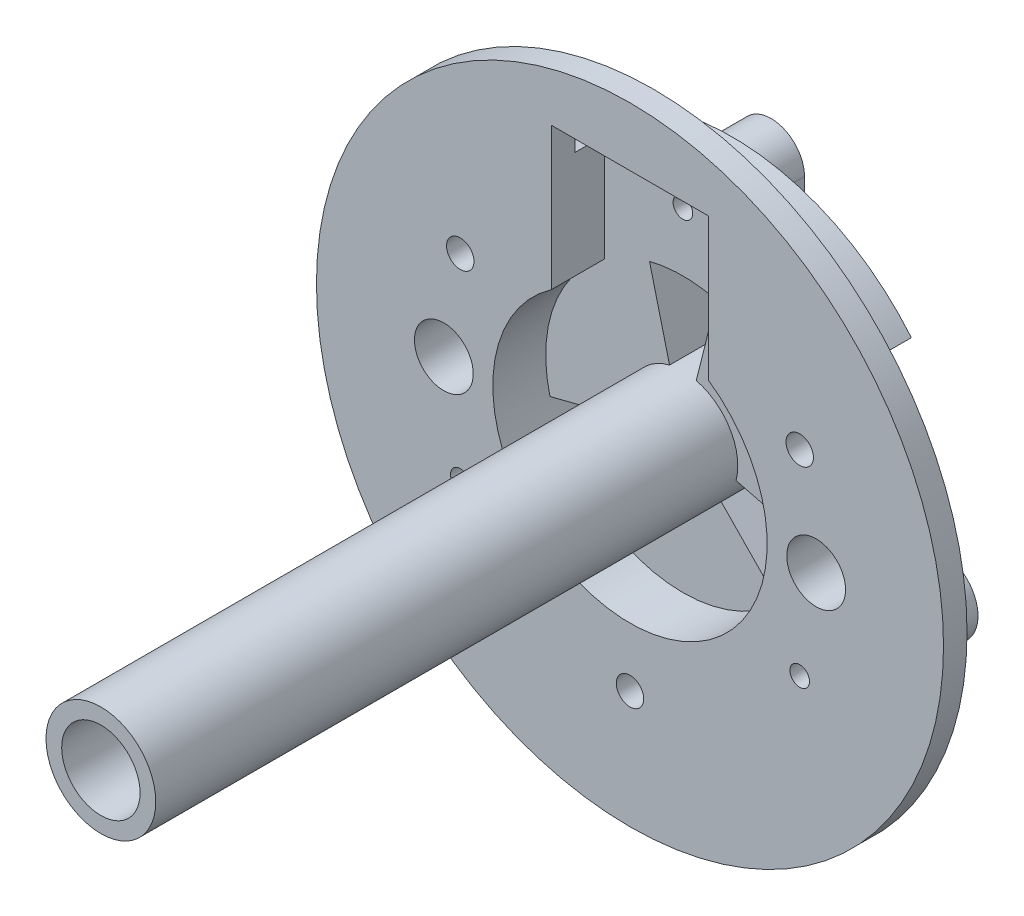
SolidWorks part; units mm, degrees
ref_plane "前视基准面" through (0, 0, 0) normal (0, 0, 1) x (1, 0, 0)
ref_plane "上视基准面" through (0, 0, 0) normal (0, 1, 0) x (1, 0, 0)
ref_plane "右视基准面" through (0, 0, 0) normal (1, 0, 0) x (0, 0, -1)
sketch "草图1" plane through (0, 0, 0) normal (0, 0, 1) x (1, 0, 0)
  circle A0 centre (0, 0) radius 16
extrude "凸台-拉伸1" add sketch "草图1" along normal blind 1.2
sketch "草图2" plane through (0, 0, 1.2) normal (0, 0, 1) x (1, 0, 0)
  circle A0 centre (0, 0) radius 7
extrude "切除-拉伸1" cut sketch "草图2" against normal blind 1.2
sketch "草图3" plane through (0, 0, 1.2) normal (0, 0, 1) x (1, 0, 0)
  circle A2 centre (8.6603, 5) radius 0.7
  circle A3 centre (0, -10) radius 0.7
  circle A4 centre (-8.6603, 5) radius 0.7
extrude "切除-拉伸2" cut sketch "草图3" against normal blind 1.2
sketch "草图4" plane through (0, 0, 0) normal (0, 0, -1) x (-1, 0, 0)
  line L3 (1.7039, 10) -> (1.7039, 5.3952)
  line L16 (-5.5379, -1.0034) -> (-3.6379, -4.2943)
  line L17 (3.6379, -4.2943) -> (5.5379, -1.0034)
  line L18 (1.7039, 5.3952) -> (-1.7039, 5.3952)
  line L19 (-5.5379, -1.0034) -> (-9.6103, -3.3546)
  line L21 (3.6379, -4.2943) -> (7.7103, -6.6454)
  line L25 (-3.6379, -4.2943) -> (-7.7103, -6.6454)
  line L31 (5.5379, -1.0034) -> (9.6103, -3.3546)
  line L32 (-1.7039, 5.3952) -> (-1.7039, 10)
  circle A1 centre (8.6603, -5) radius 0.9
  circle A2 centre (-8.6603, -5) radius 0.9
  circle A3 centre (0, 10) radius 0.9
  arc A4 (1.7039, 10) -> (-1.7039, 10) centre (0, 10) ccw
  arc A5 (7.7103, -6.6454) -> (9.6103, -3.3546) centre (8.6603, -5) ccw
  arc A6 (-9.6103, -3.3546) -> (-7.7103, -6.6454) centre (-8.6603, -5) ccw
extrude "凸台-拉伸2" add sketch "草图4" along normal blind 6
sketch "草图5" plane through (0, 0, 1.2) normal (0, 0, 1) x (1, 0, 0)
  circle A0 centre (0, 0) radius 7
extrude "切除-拉伸3" cut sketch "草图5" against normal blind 11
sketch "草图6" plane through (0, 0, 0) normal (0, 0, -1) x (-1, 0, 0)
  circle A0 centre (0, 0) radius 11.9
  circle A1 centre (0, 0) radius 7
extrude "凸台-拉伸3" add sketch "草图6" along normal blind 4
sketch "草图7" plane through (0, 0, 1.2) normal (0, 0, 1) x (1, 0, 0)
  circle A0 centre (-8.6603, 5) radius 0.7
  circle A1 centre (8.6603, 5) radius 0.7
  circle A2 centre (0, -10) radius 0.7
extrude "切除-拉伸4" cut sketch "草图7" against normal blind 13
sketch "草图8" plane through (0, 0, -4) normal (0, 0, -1) x (-1, 0, 0)
  circle A0 centre (0, 0) radius 2.8
extrude "凸台-拉伸4" add sketch "草图8" against normal blind 33 separate body
sketch "草图9" plane through (0, 0, -4) normal (0, 0, -1) x (-1, 0, 0)
  line L0 (-1.57, -1.6117) -> (-4.8846, -5.0141)
  line L1 (1.57, -1.6117) -> (4.8846, -5.0141)
  line L2 (-2.1808, -0.5539) -> (-6.7846, -1.7232)
  line L3 (-0.5477, 2.1823) -> (-1.7039, 6.7895)
  line L4 (0.5477, 2.1823) -> (1.7039, 6.7895)
  line L5 (2.1808, -0.5539) -> (6.7846, -1.7232)
  arc A0 (-4.8846, -5.0141) -> (4.8846, -5.0141) centre (0, 0) ccw
  arc A1 (-1.7039, 6.7895) -> (-6.7846, -1.7232) centre (0, 0) ccw
  arc A2 (6.7846, -1.7232) -> (1.7039, 6.7895) centre (0, 0) ccw
  arc A3 (2.1808, -0.5539) -> (0.5477, 2.1823) centre (0, 0) ccw
  arc A4 (-1.57, -1.6117) -> (1.57, -1.6117) centre (0, 0) ccw
  arc A5 (-0.5477, 2.1823) -> (-2.1808, -0.5539) centre (0, 0) ccw
extrude "凸台-拉伸5" add sketch "草图9" against normal blind 2.5
sketch "草图10" plane through (0, 0, -4) normal (0, 0, -1) x (-1, 0, 0)
  circle A0 centre (0, 0) radius 1.5
extrude "切除-拉伸5" cut sketch "草图10" against normal blind 33.5
sketch "草图12" plane through (0, 0, 0) normal (1, 0, 0) x (0, 0, -1)
  line L3 (-19.95, -5.0897) -> (-33.7637, -5.0897)
  line L4 (-19.95, -5.0897) -> (-19.95, 5.3715)
  line L5 (-19.95, 5.3715) -> (-33.7637, 5.3715)
  line L6 (-33.7637, -5.0897) -> (-33.7637, 5.3715)
extrude "切除-拉伸6" cut sketch "草图12" against normal mid plane 33.5
sketch "草图13" plane through (0, 0, -4) normal (0, 0, -1) x (-1, 0, 0)
  circle A0 centre (0, -10) radius 2
  circle A1 centre (8.6603, 5) radius 2
  circle A2 centre (-8.6603, 5) radius 2
extrude "切除-拉伸7" cut sketch "草图13" against normal blind 1.5
sketch "草图14" plane through (0, 0, 19.95) normal (0, 0, 1) x (1, 0, 0)
  circle A0 centre (0, 0) radius 2
  circle A1 centre (0, 0) radius 2.8
extrude "凸台-拉伸6" add sketch "草图14" along normal blind 8.25
sketch "草图16" plane through (0, 0, -4) normal (0, 0, -1) x (-1, 0, 0)
  line L3 (0, -10) -> (-2, -10)
  line L4 (-2, -10) -> (-2, -14.1303)
  line L5 (-2, -14.1303) -> (2, -14.1303)
  line L6 (2, -14.1303) -> (2, -10)
  line L7 (2, -10) -> (0, -10)
  line L8 (-9.6603, 3.2679) -> (-8.6603, 5)
  line L9 (-8.6603, 5) -> (-7.6603, 6.7321)
  line L10 (-7.6603, 6.7321) -> (-11.2372, 8.7972)
  line L11 (-11.2372, 8.7972) -> (-13.2372, 5.3331)
  line L12 (-13.2372, 5.3331) -> (-9.6603, 3.2679)
  line L13 (7.6603, 6.7321) -> (8.6603, 5)
  line L14 (8.6603, 5) -> (9.6603, 3.2679)
  line L15 (9.6603, 3.2679) -> (13.2372, 5.3331)
  line L16 (13.2372, 5.3331) -> (11.2372, 8.7972)
  line L17 (11.2372, 8.7972) -> (7.6603, 6.7321)
  arc A0 (0.681, -11.8805) -> (-0.681, -11.8805) centre (0, -10) ccw construction
  arc A1 (0.681, -11.8805) -> (-0.681, -11.8805) centre (0, -10) ccw construction
  point P26 (0, 0)
  dimension "D1" = 3
extrude "切除-拉伸9" cut sketch "草图16" against normal blind 1.5
sketch "草图17" plane through (0, 0, 28.2) normal (0, 0, 1) x (1, 0, 0)
  circle A0 centre (0, 0) radius 1.5
  circle A1 centre (0, 0) radius 1.48
extrude "凸台-拉伸7" add sketch "草图17" against normal blind 32.2
sketch "草图18" plane through (0, 0, 1.2) normal (0, 0, 1) x (1, 0, 0)
  line L0 (0, 13) -> (-4, 13)
  line L2 (-4, 13) -> (-4, 4.7297)
  line L3 (-4, 4.7297) -> (4, 4.7297)
  line L4 (4, 4.7297) -> (4, 13)
  line L5 (4, 13) -> (0, 13)
extrude "切除-拉伸10" cut sketch "草图18" against normal blind 2.7
sketch "草图19" plane through (0, 0, -6) normal (0, 0, -1) x (-1, 0, 0)
  circle A0 centre (-8.6603, -5) radius 0.5
  circle A1 centre (0, 10) radius 0.5
  circle A2 centre (8.6603, -5) radius 0.5
extrude "切除-拉伸11" cut sketch "草图19" against normal blind 10
sketch "草图20" plane through (0, 0, 28.2) normal (0, 0, 1) x (1, 0, 0)
  circle A0 centre (0, 0) radius 2
extrude "切除-拉伸12" cut sketch "草图20" against normal blind 45
sketch "草图22" plane through (0, 0, -4) normal (0, 0, -1) x (-1, 0, 0)
  circle A0 centre (-9.5, -0.0224) radius 1.5
  circle A2 centre (9.5, 0.0224) radius 1.5
  circle A4 centre (-0.0224, 9.5) radius 1.5 [skipped]
  circle A5 centre (0.0224, -9.5) radius 1.5 [skipped]
  point P13 (0, 0)
  dimension "D1" = 4
extrude "切除-拉伸14" cut sketch "草图22" against normal blind 10
sketch "草图23" plane through (0, 0, -4) normal (0, 0, -1) x (-1, 0, 0)
  line L0 (2.7138, -0.6893) -> (6.7846, -1.7232) construction
  arc A2 (-9.6603, 3.2679) -> (-7.6603, 6.7321) centre (-8.6603, 5) ccw construction
  spline S0 degree 3 poles (-12.7382, 6.2642) (-7.0064, 7.4648) (-6.5708, 3.731) (-6.4059, 1.2601) (-5.6212, -3.6644) (-13.5741, -3.7572) (-12.8596, 1.8066) (-12.7382, 6.2642) (-7.0064, 7.4648) (-6.5708, 3.731) knots -0.464408 -0.339652 -0.155083 0 0.061157 0.210557 0.307573 0.535592 0.660348 0.844917 1 1.061157 1.210557 1.307573 only from (-7.1212, 6.2772) to (-7.1212, 6.2772)
  spline S1 degree 3 poles (12.465, 6.4075) (7.6576, 6.8032) (6.2325, 3.9851) (6.7338, 1.478) (5.3219, -3.1557) (13.4116, -3.7472) (12.6573, 1.8143) (12.465, 6.4075) (7.6576, 6.8032) (6.2325, 3.9851) knots -0.467698 -0.336979 -0.143589 0 0.052678 0.196881 0.297625 0.532302 0.663021 0.856411 1 1.052678 1.196881 1.297625 only from (7.3923, 5.9194) to (7.3923, 5.9194)
  point P21 (-6.2765, 0.6268)
  point P27 (-6.3978, -2.01)
extrude "切除-拉伸15" cut sketch "草图23" against normal blind 1.5 and the other way blind 6.5
